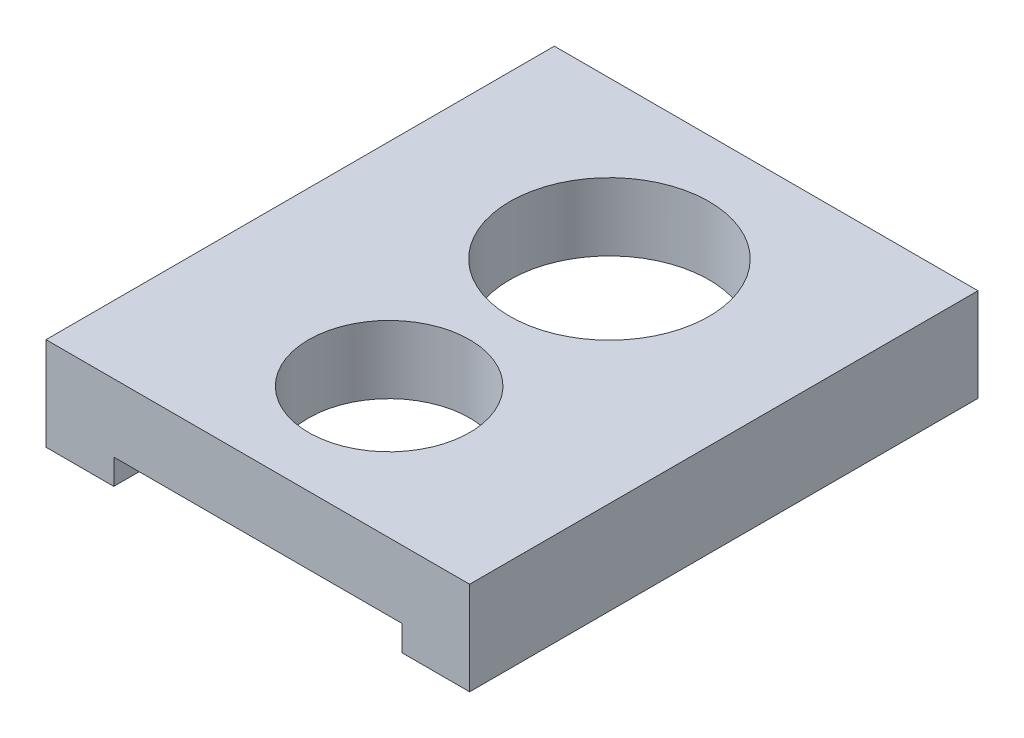
SolidWorks part; units mm, degrees
ref_plane "前基準面" through (0, 0, 0) normal (0, 0, 1) x (1, 0, 0)
ref_plane "上基準面" through (0, 0, 0) normal (0, 1, 0) x (1, 0, 0)
ref_plane "右基準面" through (0, 0, 0) normal (1, 0, 0) x (0, 0, -1)
sketch "草圖1" plane through (0, 0, 0) normal (0, 0, 1) x (1, 0, 0)
  line L0 (-25, 0) -> (-17, 0)
  line L1 (-17, 0) -> (-17, 3)
  line L2 (-17, 3) -> (17, 3)
  line L3 (17, 3) -> (17, 0)
  line L4 (17, 0) -> (25, 0)
  line L5 (25, 0) -> (25, 11)
  line L6 (25, 11) -> (-25, 11)
  line L7 (-25, 11) -> (-25, 0)
  point P3 (0, 3)
  point P10 (41.166, 31.9761)
  point P11 (-39.5317, 20.2985)
  point P12 (-34.4976, 0)
  dimension "D1" = 3
  dimension "D2" = 11
  dimension "D3" = 8
  dimension "D4" = 50
extrude "填料-伸長1" add sketch "草圖1" along normal blind 60
sketch "草圖2" plane through (0, 11, 0) normal (0, 1, 0) x (1, 0, 0)
  line L0 (25, 0) -> (-25, 0) construction
  circle A0 centre (0, -18.5) radius 11.75
  point P4 (0, 0)
  point P5 (0, 0)
  dimension "D2" = 23.5
  dimension "D1" = 18.5
extrude "除料-伸長1" cut sketch "草圖2" against normal blind 40
sketch "草圖3" plane through (0, 11, 0) normal (0, 1, 0) x (1, 0, 0)
  line L0 (25, 0) -> (-25, 0) construction
  circle A0 centre (0, -44.5) radius 9.5
  circle A1 centre (0, -18.5) radius 11.75 construction
  point P4 (0, 0)
  point P7 (0, 0)
  dimension "D1" = 26
  dimension "D2" = 19
extrude "除料-伸長2" cut sketch "草圖3" against normal blind 40
